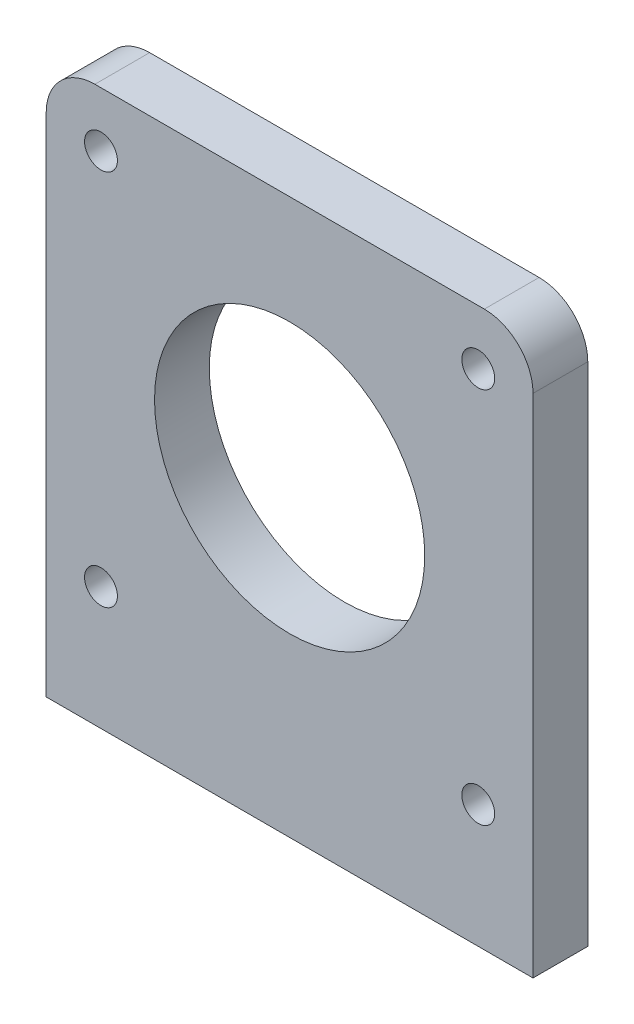
SolidWorks part; units mm, degrees
ref_plane "Front Plane" through (0, 0, 0) normal (0, 0, 1) x (1, 0, 0)
ref_plane "Top Plane" through (0, 0, 0) normal (0, 1, 0) x (1, 0, 0)
ref_plane "Right Plane" through (0, 0, 0) normal (1, 0, 0) x (0, 0, -1)
ref_axis "X Axis" through (-88.99, 0, 0) along (1, 0, 0)
ref_axis "Y Axiz" through (0, 0, 55) along (0, 0, -1)
ref_axis "Z Axis" through (0, 55, 0) along (0, -1, 0)
sketch "Sketch1" plane through (0, 0, 0) normal (0, 0, 1) x (1, 0, 0)
  line L1 (-20, 20) -> (20, 20)
  line L2 (-20, 20) -> (-20, -20)
  line L3 (-20, -20) -> (20, -20)
  line L4 (20, 20) -> (20, -20)
  line L5 (-20, 20) -> (20, -20) construction
  line L6 (-20, -20) -> (20, 20) construction
  line L7 (-20, -20) -> (20, -20)
  line L8 (-20, -20) -> (-20, -25.6)
  line L9 (-20, -25.6) -> (20, -25.6)
  line L10 (20, -20) -> (20, -25.6)
  circle A0 centre (-15.5, 15.5) radius 1.35
  circle A1 centre (15.5, 15.5) radius 1.35
  circle A2 centre (15.5, -15.5) radius 1.35
  circle A3 centre (-15.5, -15.5) radius 1.35
  circle A4 centre (0, 0) radius 11.1
  point P0 (0, 0)
  point P17 (0, 0)
  dimension "D2" = 2.7
  dimension "D7" = 22.2
  dimension "D1" = 40
  dimension "D4" = 31
  dimension "D5" = 40
  dimension "D6" = 5.6
  dimension "D3" = 4
extrude "Boss-Extrude1" add sketch "Sketch1" along normal blind 4.5 contours L10 L3 L8 L9 | L4 L1 L2 L3 A3 A2 A1 A0 region at (0, 19.4343, 0) region at (0, -22.8, 0)
fillet "Fillet1" radius 4 2 edges at (20, 20, 2.25) (-20, 20, 2.25)
